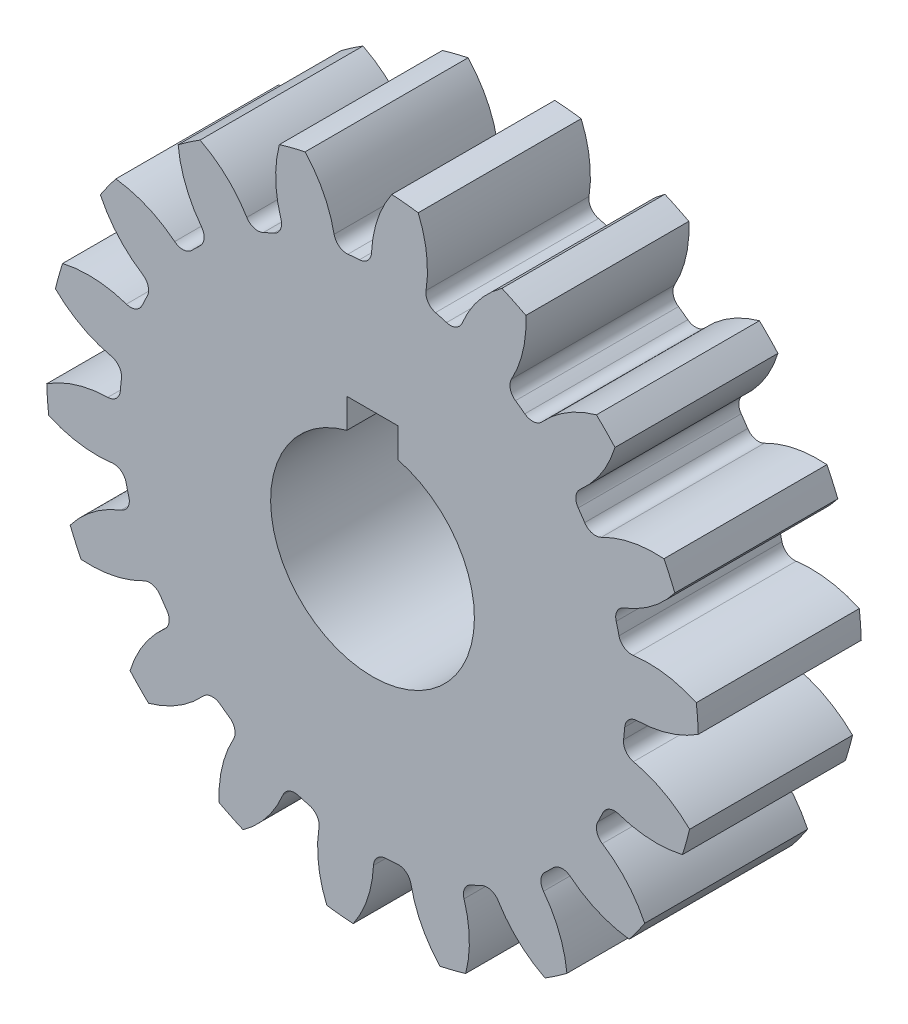
SolidWorks part; units mm, degrees
ref_plane "Front" through (0, 0, 0) normal (0, 0, 1) x (1, 0, 0)
ref_plane "Top" through (0, 0, 0) normal (0, 1, 0) x (1, 0, 0)
ref_plane "Right" through (0, 0, 0) normal (1, 0, 0) x (0, 0, -1)
sketch "Sketch3" plane through (0, 0, 0) normal (0, 0, 1) x (1, 0, 0)
  circle A0 centre (0, 0) radius 12.7
  dimension "od" = 25.4
extrude "gearBody" add sketch "Sketch3" along normal blind 6.35
sketch "Sketch2" plane through (0, 0, 0) normal (0, 0, 1) x (1, 0, 0)
  line L0 (0, 0) -> (10.2236, 4.2347) construction
  line L1 (13.3591, -4.4187) -> (0, 0) construction
  line L2 (0, 0) -> (36.3143, 0) construction
  line L3 (11.4292, -0.1374) -> (11.2291, -2.1338) construction
  line L5 (11.3291, -1.1356) -> (0, 0) construction
  line L7 (0, 0) -> (11.0659, 0) construction
  arc A0 (11.0637, -0.2221) -> (10.8877, -1.9783) centre (0, 0) ccw construction
  arc A1 (12.6927, 0.4305) -> (12.3547, -2.9412) centre (0, 0) ccw construction
  arc A2 (11.4292, -0.1374) -> (11.2291, -2.1338) centre (0, 0) ccw construction
  arc A3 (9.7812, -1.2052) -> (9.8258, -0.7602) centre (0, 0) ccw
  arc A4 (13.3591, -4.4187) -> (10.1678, -1.7534) centre (9.1796, -6.1797) ccw
  arc A5 (13.3591, -4.4187) -> (13.9704, 1.6792) centre (0, 0) ccw
  arc A6 (13.9704, 1.6792) -> (10.3136, -0.2997) centre (10.2236, 4.2347) cw
  arc A7 (9.8258, -0.7602) -> (10.3136, -0.2997) centre (10.3235, -0.7987) cw
  arc A8 (10.1678, -1.7534) -> (9.7812, -1.2052) centre (10.2766, -1.2662) cw
  point P6 (13.9704, 1.6792)
  point P22 (13.3591, -4.4187)
  dimension "baseDia" = 22.1319
  dimension "od" = 25.4
  dimension "pd" = 22.86
  dimension "rd" = 19.7104
  dimension "rFillet" = 0.4991
  dimension "pointX" = 13.9704
  dimension "pointY" = 1.6792
  dimension "CTT" = 1.9964
  dimension "flankCenterAngle" = 22.5
extrude "toothCut" cut sketch "Sketch2" along normal through all
pattern_circular "CirPattern1" count 18 over 360 about axis through (0, 0, 6.35) along (0, 0, -1) of "toothCut"
sketch "hub1Dia" plane through (0, 0, 0) normal (0, 0, -1) x (-1, 0, 0)
  circle A0 centre (0, 0) radius 25.4
  dimension "hub1Dia" = 50.8
extrude "hub1" [suppressed] add sketch "hub1Dia" along normal blind 19.05
sketch "hub2Dia" plane through (0, 0, 6.35) normal (0, 0, 1) x (1, 0, 0)
  circle A0 centre (0, 0) radius 21.844
  dimension "hub2dia" = 43.688
extrude "hub2" [suppressed] add sketch "hub2Dia" along normal blind 16.002
sketch "boreDia" plane through (0, 0, 0) normal (0, 0, 1) x (1, 0, 0)
  line L1 (-1, 3.842) -> (-1, 4.9926)
  line L2 (1, 3.842) -> (1, 4.9926)
  line L3 (-1, 4.9926) -> (1, 4.9926)
  arc A0 (-1, 3.842) -> (1, 3.842) centre (0, 0) ccw
  dimension "D1" = 2
  dimension "boreDia" = 7.94
  dimension "D2" = 1.1506
extrude "bore" cut sketch "boreDia" against normal mid plane 25.4
chamfer "hub2Chamfer" [suppressed] distance 0.508 angle 45
chamfer "hub2BoreChamfer" [suppressed] distance 0.508 angle 45
chamfer "hub1BoreChamfer" [suppressed] distance 0.508 angle 45
chamfer "hub1Chamfer" [suppressed] distance 0.508 angle 45
chamfer "BoreChamfer2" [suppressed] distance 0.508 angle 45
chamfer "boreChamfer1" [suppressed] distance 0.508 angle 45
